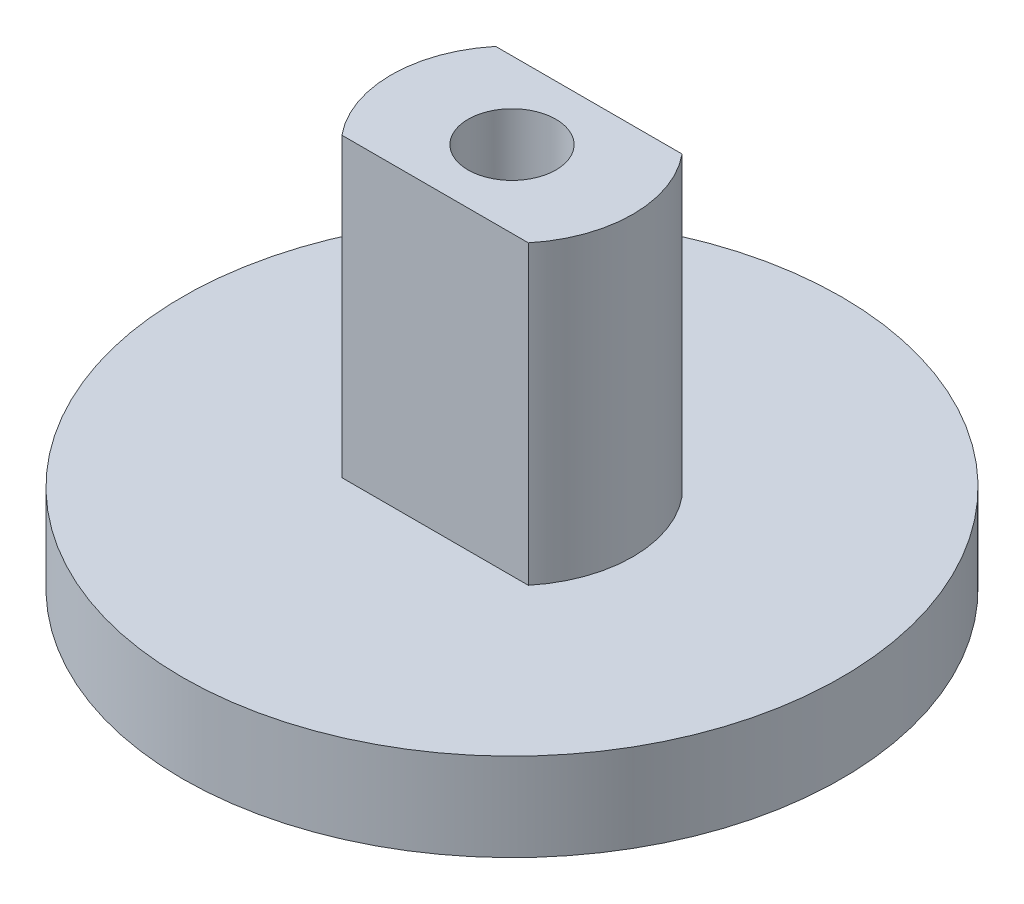
SolidWorks part; units mm, degrees
ref_plane "Front Plane" through (0, 0, 0) normal (0, 0, 1) x (1, 0, 0)
ref_plane "Top Plane" through (0, 0, 0) normal (0, 1, 0) x (1, 0, 0)
ref_plane "Right Plane" through (0, 0, 0) normal (1, 0, 0) x (0, 0, -1)
sketch "Sketch1" plane through (0, 0, 0) normal (0, 1, 0) x (1, 0, 0)
  circle A0 centre (0, 0) radius 10
extrude "Boss-Extrude2" add sketch "Sketch1" along normal blind 1
sketch "Sketch3" plane through (0, 1, 0) normal (0, 1, 0) x (1, 0, 0)
  circle A0 centre (0, 0) radius 5
extrude "Boss-Extrude3" add sketch "Sketch3" along normal blind 14
sketch "Sketch4" plane through (0, 15, 0) normal (0, 1, 0) x (1, 0, 0)
  line L0 (0, 0) -> (0, 2) construction
  line L1 (0, 2) -> (0, -2) construction
  line L3 (0, 2) -> (-4.3147, 2)
  line L4 (0, -2) -> (3.8775, -2)
  line L5 (0, -2) -> (0, 2)
  line L6 (0, 2) -> (3.8775, 2)
  line L7 (3.8775, -2) -> (3.8775, 2)
  line L8 (0, 2) -> (0, -2)
  line L9 (0, -2) -> (-4.3147, -2)
  line L10 (-4.3147, 2) -> (-4.3147, -2)
  circle A0 centre (0, 0) radius 3
extrude "Cut-Extrude1" cut sketch "Sketch4" against normal blind 19 contours L3 A0 L9 L5 | L4 A0 L6 L5 region at (-1.3889, 15, 0) region at (1.3889, 15, 0)
sketch "Sketch5" plane through (0, 1, 0) normal (0, 1, 0) x (1, 0, 0)
  circle A0 centre (0, 0) radius 12.5
extrude "Boss-Extrude4" add sketch "Sketch5" against normal up to surface (1 mm away) up to face at (0, 0, 0)
sketch "Sketch6" plane through (0, 1, 0) normal (0, 1, 0) x (1, 0, 0)
  line L4 (2.2361, 2) -> (-2.2361, 2)
  line L5 (-2.2361, -2) -> (2.2361, -2)
  line L6 (2.2361, 2) -> (-2.2361, 2)
  line L7 (-2.2361, -2) -> (2.2361, -2)
  arc A4 (-2.2361, 2) -> (-2.2361, -2) centre (0, 0) ccw
  arc A5 (2.2361, -2) -> (2.2361, 2) centre (0, 0) ccw
  arc A6 (-2.2361, 2) -> (-2.2361, -2) centre (0, 0) ccw
  arc A7 (2.2361, -2) -> (2.2361, 2) centre (0, 0) ccw
  dimension "D1" = 0
extrude "Cut-Extrude2" cut sketch "Sketch6" against normal blind 19
sketch "Sketch7" plane through (0, 15, 0) normal (0, 1, 0) x (1, 0, 0)
  line L4 (-2.2361, -2) -> (2.2361, -2)
  line L5 (2.2361, 2) -> (-2.2361, 2)
  line L6 (-2.2361, -2) -> (2.2361, -2)
  line L7 (2.2361, 2) -> (-2.2361, 2)
  circle A2 centre (0, 0) radius 5
  circle A3 centre (0, 0) radius 5
  arc A7 (2.2361, -2) -> (2.2361, 2) centre (0, 0) ccw
  arc A8 (-2.2361, 2) -> (-2.2361, -2) centre (0, 0) ccw
  arc A9 (2.2361, -2) -> (2.2361, 2) centre (0, 0) ccw
  arc A10 (-2.2361, 2) -> (-2.2361, -2) centre (0, 0) ccw
  dimension "D1" = 0
  dimension "D2" = 0
extrude "Boss-Extrude5" add sketch "Sketch7" along normal blind 2 separate body contours L6 A9 L7 A10
sketch "Sketch8" plane through (0, 17, 0) normal (0, 1, 0) x (1, 0, 0)
  circle A0 centre (0, 0) radius 7.5
extrude "Boss-Extrude6" add sketch "Sketch8" along normal blind 2
sketch "Sketch9" plane through (0, 19, 0) normal (0, 1, 0) x (1, 0, 0)
  circle A0 centre (0, 0) radius 1
extrude "Cut-Extrude3" cut sketch "Sketch9" against normal blind 25
sketch "Sketch10" plane through (0, 15, 0) normal (0, -1, 0) x (1, 0, 0)
  line L4 (-2.1213, -1.75) -> (2.1213, -1.75)
  line L5 (2.1213, 1.75) -> (-2.1213, 1.75)
  line L6 (-2.1213, -1.75) -> (2.1213, -1.75)
  line L7 (2.1213, 1.75) -> (-2.1213, 1.75)
  arc A4 (-2.1213, 1.75) -> (-2.1213, -1.75) centre (0, 0) ccw
  arc A5 (2.1213, -1.75) -> (2.1213, 1.75) centre (0, 0) ccw
  arc A6 (-2.1213, 1.75) -> (-2.1213, -1.75) centre (0, 0) ccw
  arc A7 (2.1213, -1.75) -> (2.1213, 1.75) centre (0, 0) ccw
  dimension "D1" = 0.25
extrude "Cut-Extrude4" cut sketch "Sketch10" against normal up to surface (2 mm away) up to face at (0, 17, 7.5)
sketch "Sketch11" plane through (0, 17, 0) normal (0, -1, 0) x (1, 0, 0)
  line L4 (-2.1213, -1.75) -> (2.1213, -1.75)
  line L5 (2.1213, 1.75) -> (-2.1213, 1.75)
  line L6 (-2.1213, -1.75) -> (2.1213, -1.75)
  line L7 (2.1213, 1.75) -> (-2.1213, 1.75)
  arc A4 (-2.1213, 1.75) -> (-2.1213, -1.75) centre (0, 0) ccw
  arc A5 (2.1213, -1.75) -> (2.1213, 1.75) centre (0, 0) ccw
  arc A6 (-2.1213, 1.75) -> (-2.1213, -1.75) centre (0, 0) ccw
  arc A7 (2.1213, -1.75) -> (2.1213, 1.75) centre (0, 0) ccw
  dimension "D1" = 0
extrude "Boss-Extrude7" add sketch "Sketch11" along normal blind 10
sketch "Sketch12" plane through (0, 0, 0) normal (0, -1, 0) x (1, 0, 0)
  circle A0 centre (0, 0) radius 4
  circle A3 centre (0, 0) radius 12.5
  circle A4 centre (0, 0) radius 12.5
  dimension "D1" = 0
sketch "Sketch14" plane through (0, 17, 0) normal (0, 1, 0) x (1, 0, 0)
  circle A2 centre (0, 0) radius 1
  circle A3 centre (0, 0) radius 1
  dimension "D1" = 0
extrude "Cut-Extrude5" cut sketch "Sketch14" against normal blind 18
sketch "Sketch15" plane through (0, 7, 0) normal (0, -1, 0) x (1, 0, 0)
  line L4 (-2.1213, -1.75) -> (2.1213, -1.75)
  line L5 (2.1213, 1.75) -> (-2.1213, 1.75)
  line L6 (-2.1213, -1.75) -> (2.1213, -1.75)
  line L7 (2.1213, 1.75) -> (-2.1213, 1.75)
  arc A4 (-2.1213, 1.75) -> (-2.1213, -1.75) centre (0, 0) ccw
  arc A5 (2.1213, -1.75) -> (2.1213, 1.75) centre (0, 0) ccw
  arc A6 (-2.1213, 1.75) -> (-2.1213, -1.75) centre (0, 0) ccw
  arc A7 (2.1213, -1.75) -> (2.1213, 1.75) centre (0, 0) ccw
  circle A8 centre (0, 0) radius 1
  circle A9 centre (0, 0) radius 1
  dimension "D1" = 0
  dimension "D2" = 0
extrude "Boss-Extrude8" add sketch "Sketch15" against normal blind 17
sketch "Sketch16" plane through (0, 7, 0) normal (0, -1, 0) x (1, 0, 0)
  line L4 (-2.1213, -1.75) -> (2.1213, -1.75)
  line L5 (2.1213, 1.75) -> (-2.1213, 1.75)
  line L6 (-2.1213, -1.75) -> (2.1213, -1.75)
  line L7 (2.1213, 1.75) -> (-2.1213, 1.75)
  arc A4 (-2.1213, 1.75) -> (-2.1213, -1.75) centre (0, 0) ccw
  arc A5 (2.1213, -1.75) -> (2.1213, 1.75) centre (0, 0) ccw
  arc A6 (-2.1213, 1.75) -> (-2.1213, -1.75) centre (0, 0) ccw
  arc A7 (2.1213, -1.75) -> (2.1213, 1.75) centre (0, 0) ccw
  circle A8 centre (0, 0) radius 1
  circle A9 centre (0, 0) radius 1
  dimension "D1" = 0
  dimension "D2" = 0
extrude "Cut-Extrude7" cut sketch "Sketch16" against normal up to surface (10 mm away) up to face at (0, 17, 7.5)
sketch "Sketch17" plane through (0, 15, 0) normal (0, -1, 0) x (1, 0, 0)
  line L4 (-2.2361, -2) -> (2.2361, -2)
  line L5 (2.2361, 2) -> (-2.2361, 2)
  line L6 (-2.2361, -2) -> (2.2361, -2)
  line L7 (2.2361, 2) -> (-2.2361, 2)
  arc A4 (-2.2361, 2) -> (-2.2361, -2) centre (0, 0) ccw
  arc A5 (2.2361, -2) -> (2.2361, 2) centre (0, 0) ccw
  arc A6 (-2.2361, 2) -> (-2.2361, -2) centre (0, 0) ccw
  arc A7 (2.2361, -2) -> (2.2361, 2) centre (0, 0) ccw
  dimension "D1" = 0
extrude "Cut-Extrude8" cut sketch "Sketch17" against normal up to surface (2 mm away) up to face at (0, 17, 7.5)
sketch "Sketch18" plane through (0, 17, 0) normal (0, -1, 0) x (1, 0, 0)
  circle A2 centre (0, 0) radius 7.5
  circle A3 centre (0, 0) radius 7.5
  dimension "D1" = 0
extrude "Boss-Extrude9" add sketch "Sketch18" along normal blind 1.75
sketch "Sketch19" plane through (0, 19, 0) normal (0, 1, 0) x (1, 0, 0)
  line L9 (2.1213, 1.75) -> (-2.1213, 1.75)
  line L10 (-2.1213, -1.75) -> (2.1213, -1.75)
  line L11 (2.1213, 1.75) -> (-2.1213, 1.75)
  line L12 (-2.1213, -1.75) -> (2.1213, -1.75)
  circle A0 centre (0, 0) radius 6.5
  circle A2 centre (0, 0) radius 7.5
  circle A3 centre (0, 0) radius 7.5
  arc A11 (-2.1213, 1.75) -> (-2.1213, -1.75) centre (0, 0) ccw
  arc A12 (2.1213, -1.75) -> (2.1213, 1.75) centre (0, 0) ccw
  arc A13 (-2.1213, 1.75) -> (-2.1213, -1.75) centre (0, 0) ccw
  arc A14 (2.1213, -1.75) -> (2.1213, 1.75) centre (0, 0) ccw
  arc M7 (-2.1213, -1.75) -> (-2.1213, 1.75) centre (0, 0) cw
  line M8 (-2.1213, 1.75) -> (2.1213, 1.75)
  arc M9 (2.1213, 1.75) -> (2.1213, -1.75) centre (0, 0) cw
  line M10 (2.1213, -1.75) -> (-2.1213, -1.75)
  circle M11 centre (0, 0) radius 7.5
  dimension "D1" = 0
  dimension "D2" = 1
  dimension "D3" = 0
extrude "Cut-Extrude9" cut sketch "Sketch19" against normal blind 1.75 contours A0 M11 | A0 M10 M7 M8 M9 region at (-6.3162, 19, 0) region at (-7.2879, 19, 0)
sketch "Sketch21" plane through (0, 17.25, 0) normal (0, 1, 0) x (1, 0, 0)
  circle A1 centre (0, 0) radius 12.5 construction
  circle A2 centre (0, 0) radius 7.5
  circle A3 centre (0, 0) radius 7.5
  dimension "D1" = 0
sketch "Sketch22" plane through (0, 1, 0) normal (0, 1, 0) x (1, 0, 0)
  circle A2 centre (0, 0) radius 12.5
  circle A3 centre (0, 0) radius 12.5
  dimension "D1" = 0
extrude "Cut-Extrude12" cut sketch "Sketch22" against normal blind 14 and the other way up to surface (14.25 mm away) other way up to face at (0, 15.25, -7.5)
